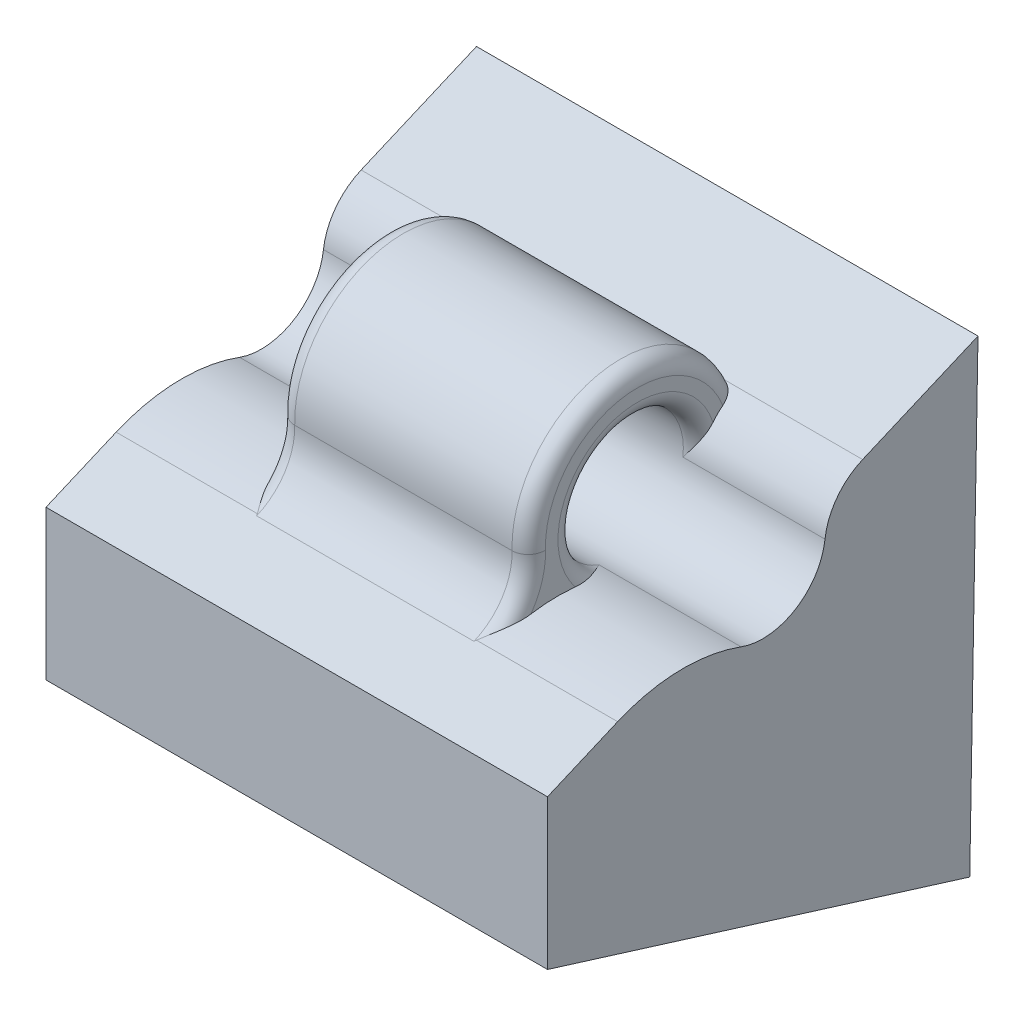
SolidWorks part; units mm, degrees
ref_plane "Front Plane" through (0, 0, 0) normal (0, 0, 1) x (1, 0, 0)
ref_plane "Top Plane" through (0, 0, 0) normal (0, 1, 0) x (1, 0, 0)
ref_plane "Right Plane" through (0, 0, 0) normal (1, 0, 0) x (0, 0, -1)
sketch "Sketch2" plane through (0, 0, 0) normal (1, 0, 0) x (0, 0, -1)
  line L0 (0, 0) -> (22.1179, 9.4423)
  line L1 (22.1179, 9.4423) -> (22.1179, 0)
  line L2 (22.1179, 0) -> (0, 0)
extrude "Boss-Extrude2" add sketch "Sketch2" along normal blind 30 and the other way blind 30 contours L0 L1 L2
sketch "Sketch3" plane through (0, 0, 0) normal (1, 0, 0) x (0, 0, -1)
  line L0 (22.0728, 9.423) -> (27.1311, 11.5825)
  line L2 (0, 0) -> (22.1179, 9.4423) construction
  line L3 (8.2773, 3.5336) -> (3.2189, 1.3742)
  arc A2 (22.0728, 9.423) -> (8.2773, 3.5336) centre (15.175, 6.4783) ccw
  arc A3 (27.1311, 11.5825) -> (3.2189, 1.3742) centre (15.175, 6.4783) ccw
  dimension "D3" = 5.5
  dimension "D1" = 15
  dimension "D2" = 9
  dimension "D4" = 5.5
extrude "Boss-Extrude4" add sketch "Sketch3" along normal blind 15 and the other way blind 15 contours A3 L3 A2 L0
sketch "Sketch4" plane through (0, 0, 0) normal (1, 0, 0) x (0, 0, -1)
  line L0 (22.1179, 0) -> (22.1179, 9.4423)
  line L1 (22.1179, 9.4423) -> (0, 0)
  line L2 (27.1311, 11.5825) -> (22.1179, 9.4423)
  line L5 (0, 0) -> (-10.5765, -4.5152)
  line L7 (0, 0) -> (22.1179, 0)
  line L8 (27.1311, 11.5825) -> (40.9266, 17.4719)
  line L9 (-10.5765, -4.5152) -> (-10.5765, -22.4121)
  line L10 (-10.5765, -22.4121) -> (39.9388, -38.0879)
  line L13 (39.9388, -38.0879) -> (40.9266, 17.4719)
  dimension "D1" = 15
  dimension "D2" = 15
extrude "Boss-Extrude5" add sketch "Sketch4" along normal blind 30 and the other way blind 30 contours L13 L8 L2 L0 L7 L5 L9 L10
sketch "Sketch5" plane through (0, 0, 0) normal (1, 0, 0) x (0, 0, -1)
  line L0 (-10.5765, -4.5152) -> (40.9266, 17.4719) construction
  circle A0 centre (15.175, 6.4783) radius 7.5
extrude "Cut-Extrude1" cut sketch "Sketch5" against normal through all both and the other way through all
fillet "Fillet1" radius 20 1 edges at (22.5, 3.5336, -8.2773)
fillet "Fillet3" radius 7.5 2 edges at (22.5, 9.423, -22.0728) (-22.5, 9.423, -22.0728)
fillet "Fillet4" radius 7.5 1 edges at (0, 0.5662, -3.5972)
fillet "Fillet6" radius 2 6 edges at (15, 1.8431, -1.0011) (-15, 1.8431, -1.0011) (15, 19.1757, -12.3861) (-15, 19.1757, -12.3861) (-15, 12.8768, -11.2622) (15, 12.8768, -11.2622)
